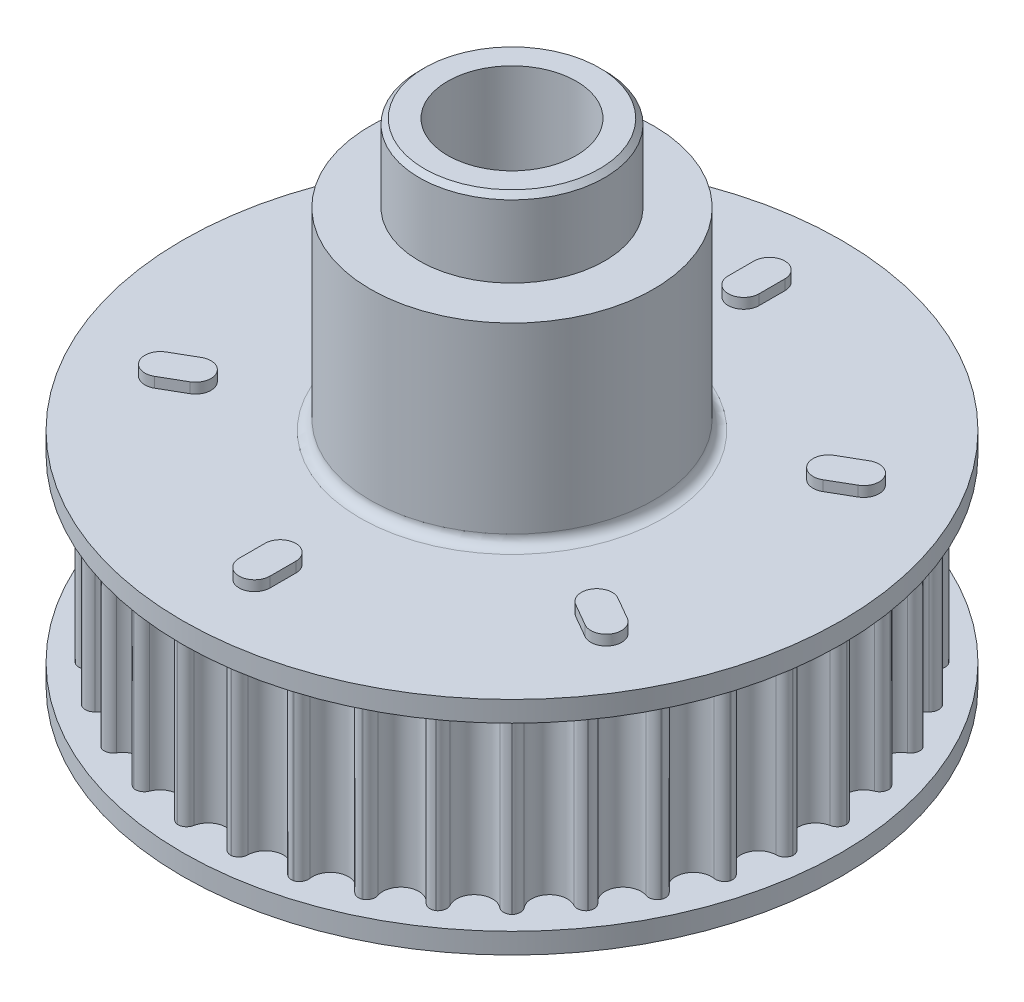
SolidWorks part; units mm, degrees
material "ABS"
ref_plane "Front Plane" through (0, 0, 0) normal (0, 0, 1) x (1, 0, 0)
ref_plane "Top Plane" through (0, 0, 0) normal (0, 1, 0) x (1, 0, 0)
ref_plane "Right Plane" through (0, 0, 0) normal (1, 0, 0) x (0, 0, -1)
sketch "Sketch1" plane through (0, 0, 0) normal (0, 1, 0) x (1, 0, 0)
  circle A0 centre (0, 0) radius 12
  circle A1 centre (0, 0) radius 2.5
  dimension "D1" = 24
  dimension "D2" = 5
extrude "Boss-Extrude1" add sketch "Sketch1" along normal blind 7
sketch "Sketch2" plane through (0, 7, 0) normal (0, 1, 0) x (1, 0, 0)
  line L0 (0, 0) -> (0, 11.8) construction
  line L1 (-1.0317, 11.955) -> (-1.2, 11.955)
  line L2 (1.0317, 11.955) -> (1.2, 11.955)
  line L3 (-1.2, 11.955) -> (-1.2, 12.1515)
  line L4 (-1.2, 12.1515) -> (1.2, 12.1515)
  line L5 (1.2, 12.1515) -> (1.2, 11.955)
  line L6 (0, 12.1515) -> (0, 12) construction
  arc A0 (-0.6878, 11.67) -> (0.6878, 11.67) centre (0, 11.8) ccw
  arc A1 (-0.6878, 11.67) -> (-1.0317, 11.955) centre (-1.0317, 11.605) ccw
  arc A2 (0.6878, 11.67) -> (1.0317, 11.955) centre (1.0317, 11.605) cw
  circle A4 centre (0, 0) radius 12 construction
  point P16 (0, 0)
  point P17 (0, 11.1)
  dimension "D3" = 0.9
  dimension "D1" = 0.7
  dimension "D2" = 0.13
  dimension "D4" = 11.8
  dimension "D6" = 0
  dimension "D7" = 1.2
  dimension "D5" = 0.35
extrude "Cut-Extrude1" cut sketch "Sketch2" against normal through all
pattern_circular "CirPattern1" count 36 over 360 about axis through (0, 7, 0) along (0, 1, 0) of "Cut-Extrude1"
sketch "Sketch4" plane through (0, 0, 0) normal (0, -1, 0) x (1, 0, 0)
  circle A0 centre (0, 0) radius 3.15
  circle A1 centre (0, 0) radius 12.8
  dimension "D1" = 25.6
extrude "Boss-Extrude4" add sketch "Sketch4" along normal blind 0.8
sketch "Sketch5" plane through (0, 7, 0) normal (0, 1, 0) x (1, 0, 0)
  circle A0 centre (0, 0) radius 2.5
  circle A1 centre (0, 0) radius 12.8
  dimension "D1" = 25.6
  dimension "D2" = 5
extrude "Boss-Extrude5" add sketch "Sketch5" along normal blind 0.8
sketch "Sketch6" plane through (0, 7.8, 0) normal (0, 1, 0) x (1, 0, 0)
  circle A0 centre (0, 0) radius 2.5
  circle A1 centre (0, 0) radius 5.5
  dimension "D1" = 11
  dimension "D2" = 5
extrude "Boss-Extrude6" add sketch "Sketch6" along normal blind 7.5
fillet "Fillet4" radius 0.4 1 edges at (0, 7.8, 5.5)
sketch "Sketch14" plane through (0, -0.8, 0) normal (0, -1, 0) x (1, 0, 0)
  circle A0 centre (0, 0) radius 4.1
  dimension "D1" = 8.2
extrude "Cut-Extrude5" cut sketch "Sketch14" against normal blind 3
sketch "Sketch16" plane through (0, 15.3, 0) normal (0, 1, 0) x (1, 0, 0)
  circle A0 centre (0, 0) radius 3.6
  circle A1 centre (0, 0) radius 2.5
  dimension "D1" = 7.2
  dimension "D2" = 5
extrude "Boss-Extrude7" add sketch "Sketch16" along normal blind 3
sketch "Sketch17" plane through (0, 2.2, 0) normal (0, -1, 0) x (1, 0, 0)
  circle A0 centre (0, 0) radius 3.6
  dimension "D1" = 7.2
extrude "Cut-Extrude6" cut sketch "Sketch17" against normal blind 1
chamfer "Chamfer1" distance 0.2 angle 45 1 edges at (0, 18.3, 3.6)
sketch "Sketch18" plane through (0, 7.8, 0) normal (0, 1, 0) x (1, 0, 0)
  line L0 (0, 9) -> (0, 10) construction
  line L1 (-0.6, 9) -> (-0.6, 10)
  line L2 (0.6, 9) -> (0.6, 10)
  line L3 (7.7942, 4.5) -> (8.6603, 5) construction
  line L4 (7.4942, 5.0196) -> (8.3603, 5.5196)
  line L5 (8.0942, 3.9804) -> (8.9603, 4.4804)
  line L6 (7.7942, -4.5) -> (8.6603, -5) construction
  line L7 (8.0942, -3.9804) -> (8.9603, -4.4804)
  line L8 (7.4942, -5.0196) -> (8.3603, -5.5196)
  line L9 (0, -9) -> (0, -10) construction
  line L10 (0.6, -9) -> (0.6, -10)
  line L11 (-0.6, -9) -> (-0.6, -10)
  line L12 (-7.7942, -4.5) -> (-8.6603, -5) construction
  line L13 (-7.4942, -5.0196) -> (-8.3603, -5.5196)
  line L14 (-8.0942, -3.9804) -> (-8.9603, -4.4804)
  line L15 (-7.7942, 4.5) -> (-8.6603, 5) construction
  line L16 (-8.0942, 3.9804) -> (-8.9603, 4.4804)
  line L17 (-7.4942, 5.0196) -> (-8.3603, 5.5196)
  arc A0 (-0.6, 9) -> (0.6, 9) centre (0, 9) ccw
  arc A1 (0.6, 10) -> (-0.6, 10) centre (0, 10) ccw
  arc A2 (7.4942, 5.0196) -> (8.0942, 3.9804) centre (7.7942, 4.5) ccw
  arc A3 (8.9603, 4.4804) -> (8.3603, 5.5196) centre (8.6603, 5) ccw
  arc A4 (8.0942, -3.9804) -> (7.4942, -5.0196) centre (7.7942, -4.5) ccw
  arc A5 (8.3603, -5.5196) -> (8.9603, -4.4804) centre (8.6603, -5) ccw
  arc A6 (0.6, -9) -> (-0.6, -9) centre (0, -9) ccw
  arc A7 (-0.6, -10) -> (0.6, -10) centre (0, -10) ccw
  arc A8 (-7.4942, -5.0196) -> (-8.0942, -3.9804) centre (-7.7942, -4.5) ccw
  arc A9 (-8.9603, -4.4804) -> (-8.3603, -5.5196) centre (-8.6603, -5) ccw
  arc A10 (-8.0942, 3.9804) -> (-7.4942, 5.0196) centre (-7.7942, 4.5) ccw
  arc A11 (-8.3603, 5.5196) -> (-8.9603, 4.4804) centre (-8.6603, 5) ccw
  point P3 (0, 9.5)
  point P13 (8.2272, 4.75)
  point P20 (8.2272, -4.75)
  point P27 (0, -9.5)
  point P34 (-8.2272, -4.75)
  point P41 (-8.2272, 4.75)
  point P46 (0, 0)
  dimension "D1" = 0.6
  dimension "D2" = 1
  dimension "D3" = 9
  dimension "D4" = 6
extrude "Boss-Extrude8" add sketch "Sketch18" along normal blind 0.4
chamfer "Chamfer2" distance 1 angle 45 1 edges at (0, 3.2, -3.6)
